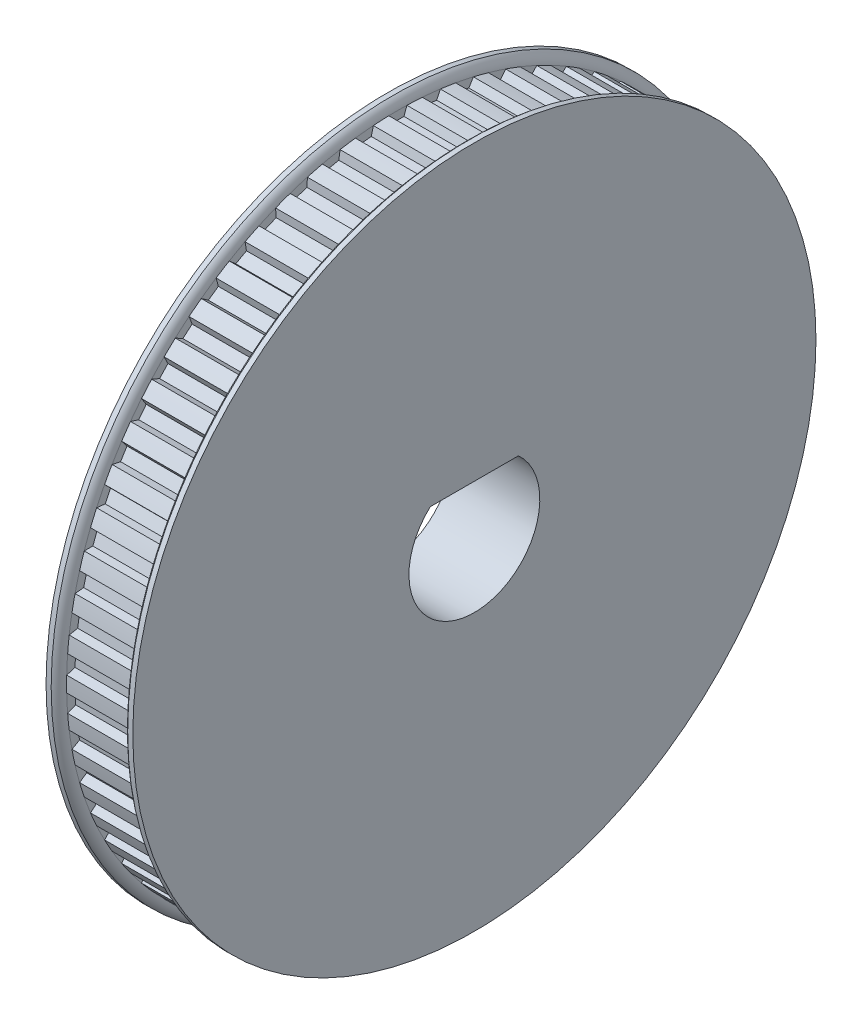
SolidWorks part; units mm, degrees
ref_plane "Front Plane" through (0, 0, 0) normal (0, 0, 1) x (1, 0, 0)
ref_plane "Top Plane" through (0, 0, 0) normal (0, 1, 0) x (1, 0, 0)
ref_plane "Right Plane" through (0, 0, 0) normal (1, 0, 0) x (0, 0, -1)
sketch "Sketch1" plane through (0, 0, 0) normal (1, 0, 0) x (0, 0, -1)
  line L3 (0, 0) -> (0, 51.285) construction
  line L6 (0, 51.285) -> (0, 52.485) construction
  line L7 (-1.325, 52.4683) -> (-0.8915, 51.2773)
  line L8 (1.325, 52.4683) -> (0.8915, 51.2773)
  line L9 (0, -2.2) -> (0, -3.2) construction
  line L10 (0, 52.985) -> (0, 52.485) construction
  line L12 (-0.8915, 51.2773) -> (0.8915, 51.2773)
  line L15 (0, 0) -> (0, -2.2) construction
  circle A0 centre (0, 0) radius 52.985 construction
  circle A1 centre (0, 0) radius 51.285 construction
  arc A7 (1.325, 52.4683) -> (-1.325, 52.4683) centre (0, 0) ccw
  dimension "PD" = 105.97
  dimension "D1" = 40
  dimension "D3" = 0.5
  dimension "D2" = 1.2
  dimension "D4" = 2.65
sketch "Sketch2" plane through (0, 0, 0) normal (0, 0, 1) x (1, 0, 0)
  line L0 (-10.5, 0) -> (10.5, 0) construction
  line L1 (-10.5, 4) -> (10.5, 4) construction
  line L2 (-10.5, 4) -> (-10.5, 19) construction
  line L3 (-2.2, 54) -> (-1.45, 54)
  line L4 (-0.7, 52.485) -> (-2.2, 52.485) construction
  line L5 (9.75, 52.485) -> (9.75, 54) construction
  line L6 (-0.7, 52.485) -> (9, 52.485)
  line L7 (-2.2, 19) -> (-2.2, 4)
  line L8 (9, 52.485) -> (10.5, 52.485) construction
  line L9 (9.75, 54) -> (10.5, 54)
  line L10 (10.5, 54) -> (10.5, 4)
  line L11 (-2.2, 4) -> (10.5, 4)
  line L12 (-6.35, 19) -> (-6.35, 4) construction
  line L13 (-2.2, 54) -> (-2.2, 19)
  line L14 (-2.2, 19) -> (-10.5, 19) construction
  arc A0 (9, 52.485) -> (9.75, 54) centre (10.9052, 52.485) cw
  arc A1 (-0.7, 52.485) -> (-1.45, 54) centre (-2.6052, 52.485) ccw
  point P19 (-0.7, 52.485)
  point P20 (9, 52.485)
  dimension "Bore Size" = 4
  dimension "Overall Width" = 21
  dimension "Inside Width" = 9.7
  dimension "Outside Width" = 12.7
  dimension "Hub Dia" = 19
  dimension "OD" = 108
sketch "Sketch6" plane through (0, 0, 0) normal (0, 0, 1) x (1, 0, 0)
  line L0 (9.75, 54) -> (10.5, 54) construction
  line L1 (-0.7, 52.485) -> (9, 52.485) construction
  line L2 (-2.2, 54) -> (-1.45, 54) construction
  line L3 (-2.2, 54) -> (-2.2, 19) construction
  line L4 (-2.2, 19) -> (-10.5, 19) construction
  line L5 (-10.5, 4) -> (-10.5, 19) construction
  line L6 (-10.5, 4) -> (10.5, 4) construction
  line L7 (10.5, 54) -> (10.5, 4) construction
  line L8 (9.75, 54) -> (10.5, 54)
  line L9 (-0.7, 52.485) -> (9, 52.485)
  line L10 (-2.2, 54) -> (-1.45, 54)
  line L11 (-2.2, 54) -> (-2.2, 19)
  line L12 (-2.2, 19) -> (-10.5, 19)
  line L13 (-10.5, 4) -> (-10.5, 19)
  line L14 (-10.5, 4) -> (10.5, 4)
  line L15 (10.5, 54) -> (10.5, 4)
  line L16 (-2.2, 19) -> (-2.2, 4)
  arc A0 (9.75, 54) -> (9, 52.485) centre (10.9052, 52.485) ccw construction
  arc A1 (-0.7, 52.485) -> (-1.45, 54) centre (-2.6052, 52.485) ccw construction
  arc A2 (9.75, 54) -> (9, 52.485) centre (10.9052, 52.485) ccw
  arc A3 (-0.7, 52.485) -> (-1.45, 54) centre (-2.6052, 52.485) ccw
revolve "Revolve1" add sketch "Sketch6" angle 360 about L14 region at (4.15, 28.3978, 0)
sketch "Sketch3" plane through (0, 0, 0) normal (1, 0, 0) x (0, 0, -1)
  line L2 (-1.325, 52.4683) -> (-0.8915, 51.2773) construction
  line L3 (-0.8915, 51.2773) -> (0.8915, 51.2773) construction
  line L4 (1.325, 52.4683) -> (0.8915, 51.2773) construction
  line L5 (-1.325, 52.4683) -> (-0.8915, 51.2773)
  line L6 (-0.8915, 51.2773) -> (0.8915, 51.2773)
  line L7 (1.325, 52.4683) -> (0.8915, 51.2773)
  arc A1 (1.325, 52.4683) -> (-1.325, 52.4683) centre (0, 0) ccw construction
  arc A2 (1.325, 52.4683) -> (-1.325, 52.4683) centre (0, 0) ccw
extrude "Cut-Extrude1" cut sketch "Sketch3" along normal up to vertex (9 mm away) from vertex up to point (9, 52.485, 0) starting at point (-0.7, 52.485, 0)
pattern_circular "CirPattern1" count 62 over 360 about axis through (-10.5, 4, 0) along (-1, 0, 0) of "Cut-Extrude1"
sketch "Sketch5" plane through (0, 0, 0) normal (0, 0, 1) x (1, 0, 0)
  line L0 (-10.5, 0) -> (10.5, 0) construction
  point P0 (9, 0)
sketch "Sketch8" plane through (-2.2, 0, 0) normal (-1, 0, 0) x (0, 0, 1)
  line L0 (-6.4545, 11.0725) -> (6.4545, 11.0725)
  arc A0 (-6.4545, 11.0725) -> (6.4545, 11.0725) centre (0, 4) ccw
  circle A1 centre (0, 4) radius 50 construction
  dimension "D1" = 19.15
  dimension "D2" = 7.0725
extrude "Cut-Extrude2" cut sketch "Sketch8" against normal through all
equation "\"D3@Sketch1\" = \"ht@Sketch1\" / 2"
equation "\"D2@Sketch1\" = \"hs@Sketch1\" - \"ht@Sketch1\""
